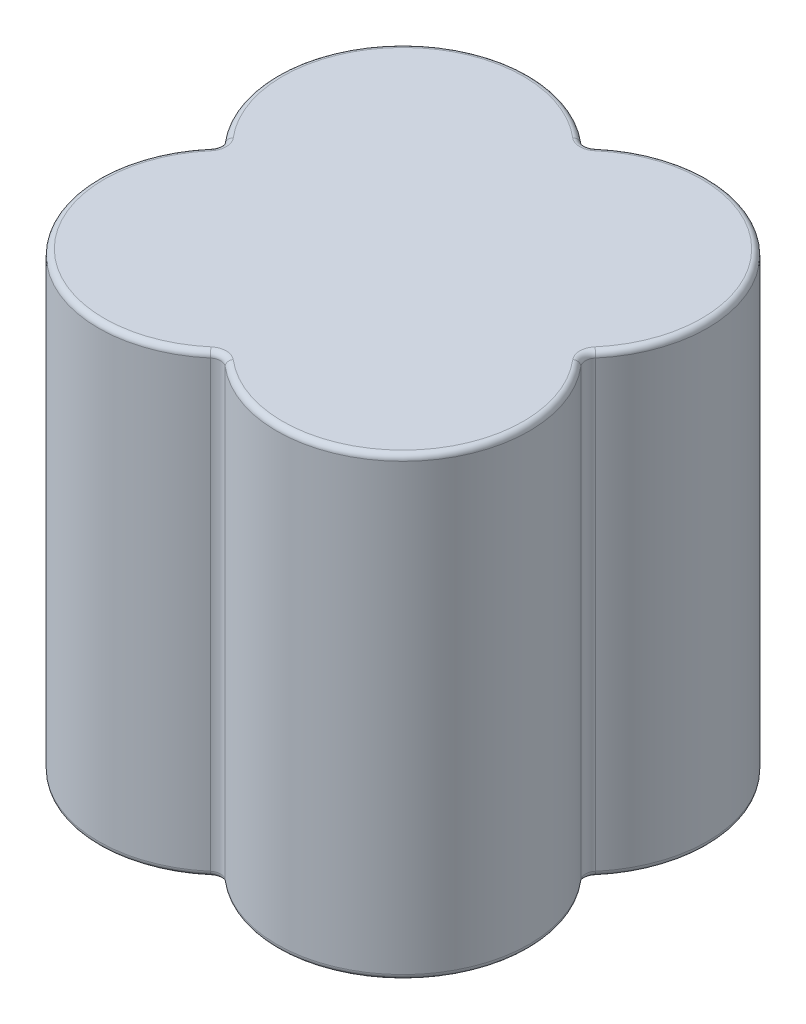
SolidWorks part; units mm, degrees
ref_plane "Front Plane" through (0, 0, 0) normal (0, 0, 1) x (1, 0, 0)
ref_plane "Top Plane" through (0, 0, 0) normal (0, 1, 0) x (1, 0, 0)
ref_plane "Right Plane" through (0, 0, 0) normal (1, 0, 0) x (0, 0, -1)
sketch "Sketch1" plane through (0, 0, 0) normal (0, 1, 0) x (1, 0, 0)
  line L0 (0, 15.6529) -> (-15.6529, 0) construction
  line L1 (-15.6529, 0) -> (0, -15.6529) construction
  line L2 (0, -15.6529) -> (15.6529, 0) construction
  line L3 (15.6529, 0) -> (0, 15.6529) construction
  line L4 (0, 0) -> (0, 39.8826) construction
  line L5 (0, 0) -> (0, -31.362) construction
  circle A0 centre (0, 0) radius 11.0683 construction
  circle A1 centre (0, 0) radius 22.1365 construction
  arc A2 (16.2516, 0.6485) -> (0.6485, 16.2516) centre (7.8264, 7.8264) ccw
  arc A3 (16.2516, -0.6485) -> (0.6485, -16.2516) centre (7.8264, -7.8264) cw
  arc A4 (-0.6485, -16.2516) -> (-16.2516, -0.6485) centre (-7.8264, -7.8264) cw
  arc A5 (-16.2516, 0.6485) -> (-0.6485, 16.2516) centre (-7.8264, 7.8264) cw
  arc A6 (-16.2516, -0.6485) -> (-16.2516, 0.6485) centre (-17.0128, 0) ccw
  arc A7 (0.6485, -16.2516) -> (-0.6485, -16.2516) centre (0, -17.0128) ccw
  arc A8 (16.2516, 0.6485) -> (16.2516, -0.6485) centre (17.0128, 0) ccw
  arc A9 (0.6485, 16.2516) -> (-0.6485, 16.2516) centre (0, 17.0128) cw
  dimension "D1" = 1
  dimension "D2" = 44.2731
extrude "Boss-Extrude1" add sketch "Sketch1" along normal blind 40
fillet "Fillet1" radius 0.5 16 edges at (-15.6529, 0, 15.6529) (0, 0, 16.0128) (15.6529, 0, 15.6529) (16.0128, 0, 0) (15.6529, 0, -15.6529) (0, 0, -16.0128) (-15.6529, 0, -15.6529) (-16.0128, 0, 0) (-15.6529, 40, -15.6529) (0, 40, -16.0128) (15.6529, 40, -15.6529) (16.0128, 40, 0) (15.6529, 40, 15.6529) (0, 40, 16.0128) (-15.6529, 40, 15.6529) (-16.0128, 40, 0)
